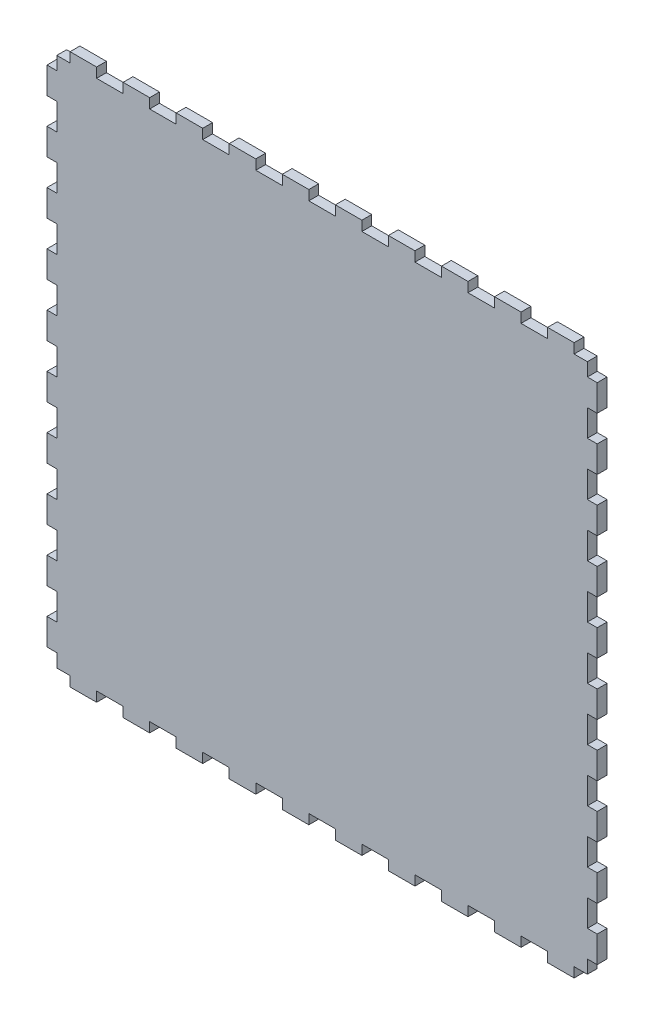
SolidWorks part; units mm, degrees
ref_plane "Front Plane" through (0, 0, 0) normal (0, 0, 1) x (1, 0, 0)
ref_plane "Top Plane" through (0, 0, 0) normal (0, 1, 0) x (1, 0, 0)
ref_plane "Right Plane" through (0, 0, 0) normal (1, 0, 0) x (0, 0, -1)
sketch "Sketch1" plane through (0, 0, 0) normal (0, 0, 1) x (1, 0, 0)
  line L0 (6.35, 349.25) -> (6.35, 6.35) construction
  line L1 (0, 0) -> (355.6, 0) construction
  line L2 (0, 0) -> (0, 355.6) construction
  line L3 (0, 355.6) -> (355.6, 355.6) construction
  line L4 (355.6, 0) -> (355.6, 355.6) construction
  line L5 (0, 6.35) -> (349.25, 6.35) construction
  line L6 (0, 349.25) -> (349.25, 349.25) construction
  line L7 (349.25, 349.25) -> (349.25, 0) construction
  line L8 (6.35, 349.25) -> (14.9225, 349.25)
  line L9 (14.9225, 349.25) -> (14.9225, 355.6)
  line L10 (14.9225, 355.6) -> (32.0675, 355.6)
  line L11 (32.0675, 355.6) -> (32.0675, 349.25)
  line L12 (32.0675, 349.25) -> (49.2125, 349.25)
  line L13 (14.9225, 355.6) -> (32.0675, 355.6)
  line L14 (66.3575, 349.25) -> (83.5025, 349.25)
  line L15 (66.3575, 355.6) -> (66.3575, 349.25)
  line L16 (49.2125, 355.6) -> (66.3575, 355.6)
  line L17 (49.2125, 349.25) -> (49.2125, 355.6)
  line L18 (100.6475, 349.25) -> (117.7925, 349.25)
  line L19 (100.6475, 355.6) -> (100.6475, 349.25)
  line L20 (83.5025, 355.6) -> (100.6475, 355.6)
  line L21 (83.5025, 349.25) -> (83.5025, 355.6)
  line L22 (134.9375, 349.25) -> (152.0825, 349.25)
  line L23 (134.9375, 355.6) -> (134.9375, 349.25)
  line L24 (117.7925, 355.6) -> (134.9375, 355.6)
  line L25 (117.7925, 349.25) -> (117.7925, 355.6)
  line L26 (169.2275, 349.25) -> (186.3725, 349.25)
  line L27 (169.2275, 355.6) -> (169.2275, 349.25)
  line L28 (152.0825, 355.6) -> (169.2275, 355.6)
  line L29 (152.0825, 349.25) -> (152.0825, 355.6)
  line L30 (203.5175, 349.25) -> (220.6625, 349.25)
  line L31 (203.5175, 355.6) -> (203.5175, 349.25)
  line L32 (186.3725, 355.6) -> (203.5175, 355.6)
  line L33 (186.3725, 349.25) -> (186.3725, 355.6)
  line L34 (237.8075, 349.25) -> (254.9525, 349.25)
  line L35 (237.8075, 355.6) -> (237.8075, 349.25)
  line L36 (220.6625, 355.6) -> (237.8075, 355.6)
  line L37 (220.6625, 349.25) -> (220.6625, 355.6)
  line L38 (272.0975, 349.25) -> (289.2425, 349.25)
  line L39 (272.0975, 355.6) -> (272.0975, 349.25)
  line L40 (254.9525, 355.6) -> (272.0975, 355.6)
  line L41 (254.9525, 349.25) -> (254.9525, 355.6)
  line L42 (306.3875, 349.25) -> (323.5325, 349.25)
  line L43 (306.3875, 355.6) -> (306.3875, 349.25)
  line L44 (289.2425, 355.6) -> (306.3875, 355.6)
  line L45 (289.2425, 349.25) -> (289.2425, 355.6)
  line L46 (340.6775, 349.25) -> (349.25, 349.25)
  line L47 (340.6775, 355.6) -> (340.6775, 349.25)
  line L48 (323.5325, 355.6) -> (340.6775, 355.6)
  line L49 (323.5325, 349.25) -> (323.5325, 355.6)
  line L50 (6.35, 349.25) -> (6.35, 340.6775)
  line L51 (6.35, 340.6775) -> (0, 340.6775)
  line L52 (0, 340.6775) -> (0, 323.5325)
  line L53 (0, 323.5325) -> (6.35, 323.5325)
  line L54 (6.35, 323.5325) -> (6.35, 306.3875)
  line L55 (6.35, 289.2425) -> (6.35, 272.0975)
  line L56 (0, 289.2425) -> (6.35, 289.2425)
  line L57 (0, 306.3875) -> (0, 289.2425)
  line L58 (6.35, 306.3875) -> (0, 306.3875)
  line L59 (6.35, 254.9525) -> (6.35, 237.8075)
  line L60 (0, 254.9525) -> (6.35, 254.9525)
  line L61 (0, 272.0975) -> (0, 254.9525)
  line L62 (6.35, 272.0975) -> (0, 272.0975)
  line L63 (6.35, 220.6625) -> (6.35, 203.5175)
  line L64 (0, 220.6625) -> (6.35, 220.6625)
  line L65 (0, 237.8075) -> (0, 220.6625)
  line L66 (6.35, 237.8075) -> (0, 237.8075)
  line L67 (6.35, 186.3725) -> (6.35, 169.2275)
  line L68 (0, 186.3725) -> (6.35, 186.3725)
  line L69 (0, 203.5175) -> (0, 186.3725)
  line L70 (6.35, 203.5175) -> (0, 203.5175)
  line L71 (6.35, 152.0825) -> (6.35, 134.9375)
  line L72 (0, 152.0825) -> (6.35, 152.0825)
  line L73 (0, 169.2275) -> (0, 152.0825)
  line L74 (6.35, 169.2275) -> (0, 169.2275)
  line L75 (6.35, 117.7925) -> (6.35, 100.6475)
  line L76 (0, 117.7925) -> (6.35, 117.7925)
  line L77 (0, 134.9375) -> (0, 117.7925)
  line L78 (6.35, 134.9375) -> (0, 134.9375)
  line L79 (6.35, 83.5025) -> (6.35, 66.3575)
  line L80 (0, 83.5025) -> (6.35, 83.5025)
  line L81 (0, 100.6475) -> (0, 83.5025)
  line L82 (6.35, 100.6475) -> (0, 100.6475)
  line L83 (6.35, 49.2125) -> (6.35, 32.0675)
  line L84 (0, 49.2125) -> (6.35, 49.2125)
  line L85 (0, 66.3575) -> (0, 49.2125)
  line L86 (6.35, 66.3575) -> (0, 66.3575)
  line L87 (6.35, 14.9225) -> (6.35, 6.35)
  line L88 (0, 14.9225) -> (6.35, 14.9225)
  line L89 (0, 32.0675) -> (0, 14.9225)
  line L90 (6.35, 32.0675) -> (0, 32.0675)
  line L91 (6.35, 6.35) -> (14.9225, 6.35)
  line L92 (14.9225, 6.35) -> (14.9225, 0)
  line L93 (14.9225, 0) -> (32.0675, 0)
  line L94 (32.0675, 0) -> (32.0675, 6.35)
  line L95 (32.0675, 6.35) -> (49.2125, 6.35)
  line L96 (66.3575, 6.35) -> (83.5025, 6.35)
  line L97 (66.3575, 0) -> (66.3575, 6.35)
  line L98 (49.2125, 0) -> (66.3575, 0)
  line L99 (49.2125, 6.35) -> (49.2125, 0)
  line L100 (100.6475, 6.35) -> (117.7925, 6.35)
  line L101 (100.6475, 0) -> (100.6475, 6.35)
  line L102 (83.5025, 0) -> (100.6475, 0)
  line L103 (83.5025, 6.35) -> (83.5025, 0)
  line L104 (134.9375, 6.35) -> (152.0825, 6.35)
  line L105 (134.9375, 0) -> (134.9375, 6.35)
  line L106 (117.7925, 0) -> (134.9375, 0)
  line L107 (117.7925, 6.35) -> (117.7925, 0)
  line L108 (169.2275, 6.35) -> (186.3725, 6.35)
  line L109 (169.2275, 0) -> (169.2275, 6.35)
  line L110 (152.0825, 0) -> (169.2275, 0)
  line L111 (152.0825, 6.35) -> (152.0825, 0)
  line L112 (203.5175, 6.35) -> (220.6625, 6.35)
  line L113 (203.5175, 0) -> (203.5175, 6.35)
  line L114 (186.3725, 0) -> (203.5175, 0)
  line L115 (186.3725, 6.35) -> (186.3725, 0)
  line L116 (237.8075, 6.35) -> (254.9525, 6.35)
  line L117 (237.8075, 0) -> (237.8075, 6.35)
  line L118 (220.6625, 0) -> (237.8075, 0)
  line L119 (220.6625, 6.35) -> (220.6625, 0)
  line L120 (272.0975, 6.35) -> (289.2425, 6.35)
  line L121 (272.0975, 0) -> (272.0975, 6.35)
  line L122 (254.9525, 0) -> (272.0975, 0)
  line L123 (254.9525, 6.35) -> (254.9525, 0)
  line L124 (306.3875, 6.35) -> (323.5325, 6.35)
  line L125 (306.3875, 0) -> (306.3875, 6.35)
  line L126 (289.2425, 0) -> (306.3875, 0)
  line L127 (289.2425, 6.35) -> (289.2425, 0)
  line L128 (340.6775, 6.35) -> (349.25, 6.35)
  line L129 (340.6775, 0) -> (340.6775, 6.35)
  line L130 (323.5325, 0) -> (340.6775, 0)
  line L131 (323.5325, 6.35) -> (323.5325, 0)
  line L132 (349.25, 6.35) -> (349.25, 14.9225)
  line L133 (349.25, 14.9225) -> (355.6, 14.9225)
  line L134 (355.6, 14.9225) -> (355.6, 32.0675)
  line L135 (355.6, 32.0675) -> (349.25, 32.0675)
  line L136 (349.25, 32.0675) -> (349.25, 49.2125)
  line L137 (349.25, 66.3575) -> (349.25, 83.5025)
  line L138 (355.6, 66.3575) -> (349.25, 66.3575)
  line L139 (355.6, 49.2125) -> (355.6, 66.3575)
  line L140 (349.25, 49.2125) -> (355.6, 49.2125)
  line L141 (349.25, 100.6475) -> (349.25, 117.7925)
  line L142 (355.6, 100.6475) -> (349.25, 100.6475)
  line L143 (355.6, 83.5025) -> (355.6, 100.6475)
  line L144 (349.25, 83.5025) -> (355.6, 83.5025)
  line L145 (349.25, 134.9375) -> (349.25, 152.0825)
  line L146 (355.6, 134.9375) -> (349.25, 134.9375)
  line L147 (355.6, 117.7925) -> (355.6, 134.9375)
  line L148 (349.25, 117.7925) -> (355.6, 117.7925)
  line L149 (349.25, 169.2275) -> (349.25, 186.3725)
  line L150 (355.6, 169.2275) -> (349.25, 169.2275)
  line L151 (355.6, 152.0825) -> (355.6, 169.2275)
  line L152 (349.25, 152.0825) -> (355.6, 152.0825)
  line L153 (349.25, 203.5175) -> (349.25, 220.6625)
  line L154 (355.6, 203.5175) -> (349.25, 203.5175)
  line L155 (355.6, 186.3725) -> (355.6, 203.5175)
  line L156 (349.25, 186.3725) -> (355.6, 186.3725)
  line L157 (349.25, 237.8075) -> (349.25, 254.9525)
  line L158 (355.6, 237.8075) -> (349.25, 237.8075)
  line L159 (355.6, 220.6625) -> (355.6, 237.8075)
  line L160 (349.25, 220.6625) -> (355.6, 220.6625)
  line L161 (349.25, 272.0975) -> (349.25, 289.2425)
  line L162 (355.6, 272.0975) -> (349.25, 272.0975)
  line L163 (355.6, 254.9525) -> (355.6, 272.0975)
  line L164 (349.25, 254.9525) -> (355.6, 254.9525)
  line L165 (349.25, 306.3875) -> (349.25, 323.5325)
  line L166 (355.6, 306.3875) -> (349.25, 306.3875)
  line L167 (355.6, 289.2425) -> (355.6, 306.3875)
  line L168 (349.25, 289.2425) -> (355.6, 289.2425)
  line L169 (349.25, 340.6775) -> (349.25, 349.25)
  line L170 (355.6, 340.6775) -> (349.25, 340.6775)
  line L171 (355.6, 323.5325) -> (355.6, 340.6775)
  line L172 (349.25, 323.5325) -> (355.6, 323.5325)
  dimension "D1" = 355.6
  dimension "D2" = 355.6
  dimension "D3" = 6.35
  dimension "D4" = 6.35
  dimension "D5" = 10
  dimension "D6" = 6.35
  dimension "D7" = 8.5725
  dimension "D8" = 17.145
  dimension "D9" = 17.145
  dimension "D10" = 10
  dimension "D11" = 10
  dimension "D12" = 10
extrude "Boss-Extrude1" add sketch "Sketch1" along normal blind 6.35 contours L165 L172 L171 L170 L169 L46 L47 L48 L49 L42 L43 L44 L45 L38 L39 L40 L41 L34 L35 L36 L37 L30 L31 L32 L33 L26 L27 L28 L29 L22 L23 L24 L25 L18 L19 L20 L21 L14 L15 L16 L17 L12 L11 L10 L9 L8 L50 L51 L52 L53 L54 region at (177.8, 177.8, 0)
